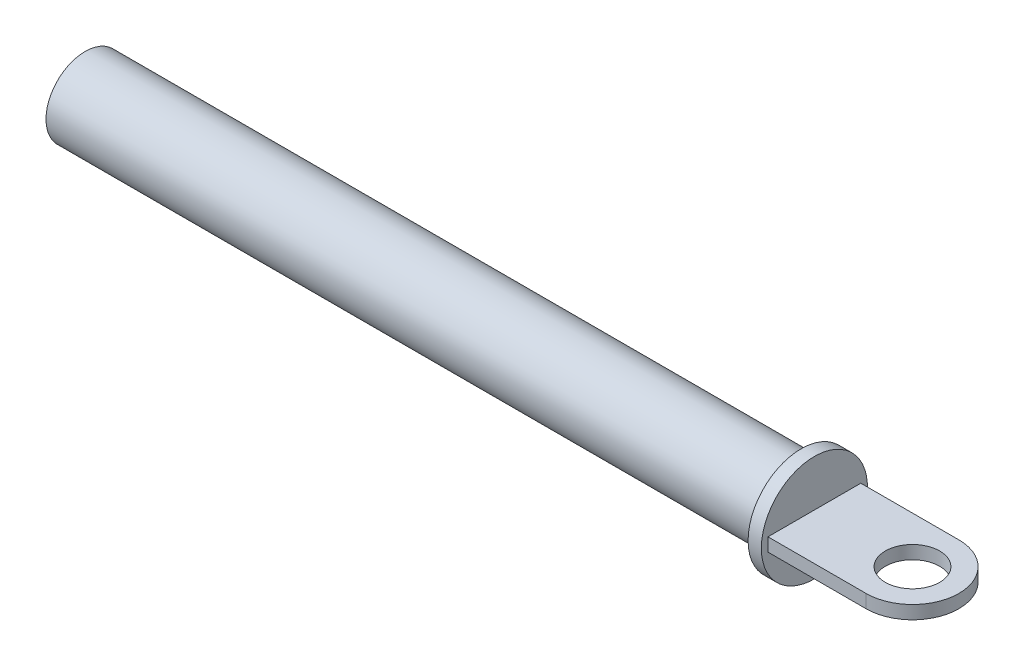
SolidWorks part; units mm, degrees
ref_plane "Front Plane" through (0, 0, 0) normal (0, 0, 1) x (1, 0, 0)
ref_plane "Top Plane" through (0, 0, 0) normal (0, 1, 0) x (1, 0, 0)
ref_plane "Right Plane" through (0, 0, 0) normal (1, 0, 0) x (0, 0, -1)
ref_plane "Plane1" through (0, 0, 0) normal (0, 0, -1) x (-1, 0, 0)
sketch "Sketch1" plane through (0, 0, 0) normal (0, 0, -1) x (-1, 0, 0)
  line L0 (-33, 4) -> (-33, 0)
  line L1 (-33, 0) -> (-32, 0)
  line L2 (-32, 0) -> (-32, 4)
  line L3 (-32, 4) -> (-33, 4)
  line L4 (-33, 0) -> (-32, 0) construction
  point P4 (0, 0)
  dimension "D1" = 4
  dimension "D2" = 1
  dimension "D3" = 32
revolve "Revolve1" add sketch "Sketch1" angle 360 about L4 reverse direction yes
ref_plane "Plane2" through (0, 0.5, 0) normal (0, 1, 0) x (1, 0, 0)
sketch "Sketch2" plane through (0, 0.5, 0) normal (0, 1, 0) x (1, 0, 0)
  line L0 (33, 3.5) -> (33, -3.5)
  line L1 (33, -3.5) -> (40.3984, -3.5)
  line L2 (40.3984, 3.5) -> (33, 3.5)
  line L3 (33, 0) -> (32, 0) construction
  line L4 (32, 4) -> (32, -4) construction
  line L7 (33, -4) -> (33, 4) construction
  arc A0 (40.3984, -3.5) -> (40.3984, 3.5) centre (40.3984, 0) ccw
  point P7 (0, 0)
  dimension "D2" = 3.5
  dimension "D1" = 7.3984
extrude "Boss-Extrude1" add sketch "Sketch2" against normal blind 1
sketch "Sketch3" plane through (32, 0, 0) normal (-1, 0, 0) x (0, 0, 1)
  circle A0 centre (0, 0) radius 2.95
  circle A1 centre (0, 0) radius 4 construction
  point P2 (0, 0)
  point P3 (0.7683, -0.4734)
  dimension "D1" = 5.9
extrude "Boss-Extrude2" add sketch "Sketch3" along normal blind 54
hole_wizard "Ø4.1 (4.1) Diameter Hole1" positions "Sketch5" profile "Sketch4" hole size "Ø4.1" standard "ANSI Metric" end condition through all
sketch "Sketch5" plane through (0, -0.5, 0) normal (0, -1, 0) x (-1, 0, 0)
  arc A0 (-40.3984, 3.5) -> (-40.3984, -3.5) centre (-40.3984, 0) ccw construction
  point P0 (-40.3984, 0)
  point P1 (0, 0)
sketch "Sketch4" plane through (40.3984, -0.5, 0) normal (1, 0, 0) x (0, 0, -1)
  line L0 (0, 0) -> (0, 4.5)
  line L1 (0, 4.5) -> (2.05, 4.5)
  line L2 (2.05, 4.5) -> (2.05, 0)
  line L5 (2.05, 0) -> (0, 0)
  line L11 (0, -6.35) -> (0, 107.95) construction
  dimension "Thru Hole Dia." = 4.1
  dimension "Thru Hole Depth" = 4.5
ref_axis "Axis1" through (40.3984, 10.9013, 0) along (0, -1, 0)
